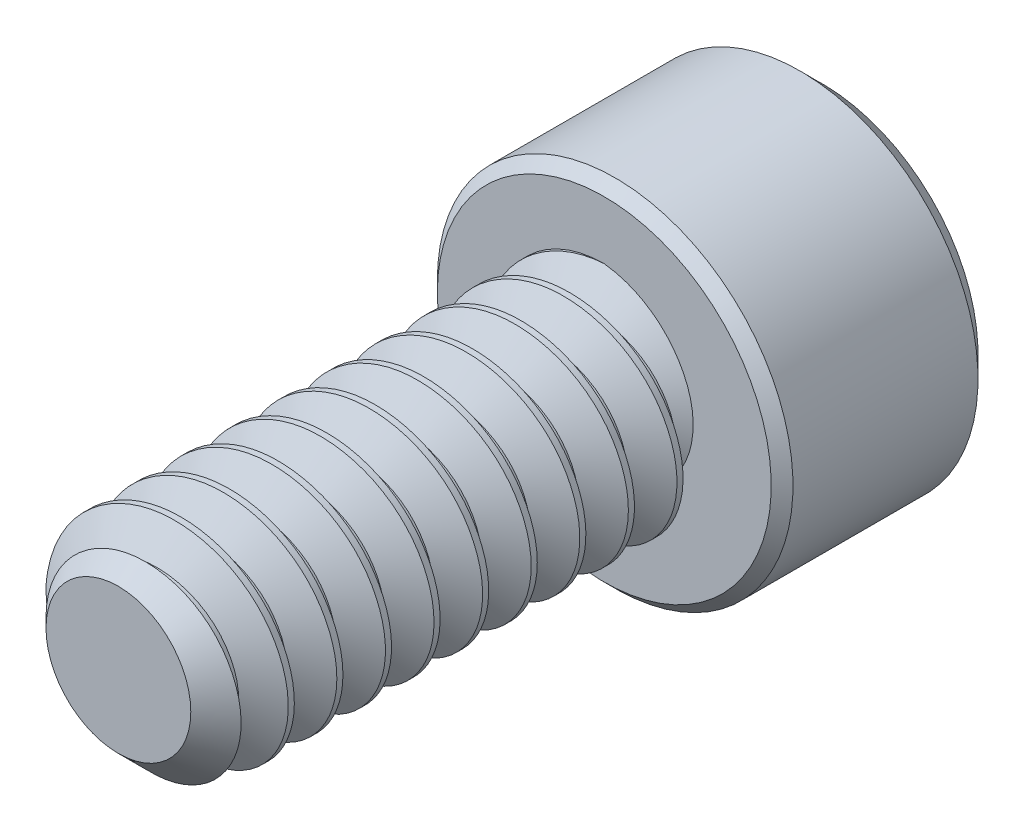
SolidWorks part; units mm, degrees
ref_plane "Front Plane" through (0, 0, 0) normal (0, 0, 1) x (1, 0, 0)
ref_plane "Top Plane" through (0, 0, 0) normal (0, 1, 0) x (1, 0, 0)
ref_plane "Right Plane" through (0, 0, 0) normal (1, 0, 0) x (0, 0, -1)
sketch "Sketch1" plane through (0, 0, 0) normal (0, 0, 1) x (1, 0, 0)
  line L0 (0, 1.4224) -> (0, -1.4224) construction
  circle A0 centre (0, 0) radius 1.4224
  dimension "OD" = 2.8448
extrude "Extrude1" add sketch "Sketch1" against normal blind 6.35
sketch "Sketch2" plane through (0, 0, 0) normal (0, 0, 1) x (1, 0, 0)
  circle A0 centre (0, 0) radius 1.4224 construction
  circle A1 centre (0, 0) radius 1.4224
curve "Helix/Spiral1" pitch 0.635 height 6.985 radius 1.4224 centre (0, 0, 0) axis (0, 0, -1) start towards (0, 1, 0) parameters "pitch"=0.635
chamfer "Chamfer3" distance 0.4763 angle 45 1 edges at (1.4224, 0, 0)
sketch "Sketch3" plane through (0, 0, 0) normal (1, 0, 0) x (0, 0, -1)
  line L0 (-0.5556, 1.4224) -> (-0.3175, 1.01)
  line L1 (-0.3175, 1.01) -> (-0.2381, 1.01)
  line L2 (-0.2381, 1.01) -> (0, 1.4224)
  line L3 (-0.5556, 1.4224) -> (0, 1.4224)
  line L4 (-0.2778, 1.4224) -> (-0.2778, 1.01) construction
  line L5 (-0.4366, 1.2162) -> (-0.1191, 1.2162) construction
  line L6 (0, 1.4224) -> (0, -1.4224) construction
  dimension "D1" = 0.0794
  dimension "D2" = 0.3175
  dimension "D3" = 60
sweep "Cut-Sweep1" cut profiles "Sketch3" path "Helix/Spiral1" align with end faces yes
sketch "Sketch6" plane through (0, 0, -6.35) normal (0, 0, -1) x (-1, 0, 0)
  circle A0 centre (0, 0) radius 2.3241
  dimension "head dia" = 4.6482
extrude "Extrude2" add sketch "Sketch6" along normal blind 2.8448
sketch "Sketch7" plane through (0, 0, -9.1948) normal (0, 0, -1) x (-1, 0, 0)
  line L1 (0, 1.3748) -> (-1.1906, 0.6874)
  line L2 (-1.1906, 0.6874) -> (-1.1906, -0.6874)
  line L3 (-1.1906, -0.6874) -> (0, -1.3748)
  line L4 (0, -1.3748) -> (1.1906, -0.6874)
  line L5 (1.1906, -0.6874) -> (1.1906, 0.6874)
  line L6 (1.1906, 0.6874) -> (0, 1.3748)
  circle A0 centre (0, 0) radius 1.1906 construction
  dimension "hex dia" = 2.3813
extrude "Cut-Extrude1" cut sketch "Sketch7" against normal blind 1.7859
sketch "Sketch8" plane through (0, 0, -9.1948) normal (0, 0, -1) x (-1, 0, 0)
  circle A0 centre (0, 0) radius 1.3748
extrude "Cut-Extrude2" cut sketch "Sketch8" against normal blind 0.2845 draft 45
chamfer "Chamfer1" distance 0.2845 angle 45 1 edges at (-2.3241, 0, -9.1948)
chamfer "Chamfer2" distance 0.1422 angle 45 1 edges at (-2.3241, 0, -6.35)
sketch "Sketch9" plane through (0, 0, 0) normal (1, 0, 0) x (0, 0, -1)
  line L0 (0, 1.4224) -> (0, -1.4224) construction
  line L1 (3.4925, 1.4224) -> (3.4925, -1.4224) construction
  line L2 (6.35, 2.3241) -> (6.35, -2.3241) construction
  line L3 (9.1948, 2.3241) -> (9.1948, -2.3241) construction
  line L4 (9.1948, 0) -> (0, 0) construction
  dimension "D1" = 3.4925
  dimension "D2" = 2.8448
  dimension "D3" = 4.6482
  dimension "D4" = 6.35
equation "\"D3@Helix/Spiral1\" = \"screw length@Extrude1\"+\"pitch@Helix/Spiral1\""
equation "\"D1@Sketch3\" = \"pitch@Helix/Spiral1\"*.125"
equation "\"D2@Sketch3\" = \"pitch@Helix/Spiral1\"*.5"
equation "\"D1@Cut-Extrude1\" = \"hex dia@Sketch7\"*.75"
equation "\"D1@Chamfer1\" = \"head depth@Extrude2\"/10"
equation "\"D1@Sketch9\" = \"pitch@Helix/Spiral1\"*5.5"
equation "\"D1@Chamfer2\" = \"D1@Chamfer1\"/2"
equation "\"D1@Cut-Extrude2\" = \"D1@Chamfer2\"*2"
equation "\"D1@Chamfer3\" = \"pitch@Helix/Spiral1\"*.750"
equation "\"D2@Sketch9\" = \"head depth@Extrude2\""
equation "\"D3@Sketch9\" = \"head dia@Sketch6\""
equation "\"D4@Sketch9\" = \"screw length@Extrude1\""
